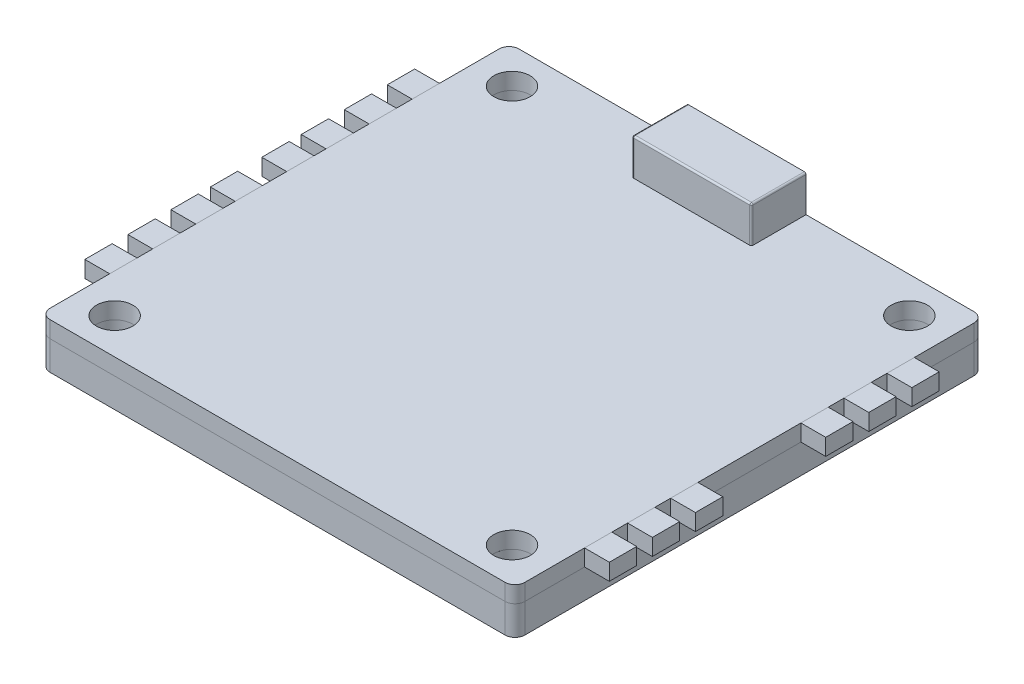
SolidWorks part; units mm, degrees
ref_plane "Front" through (0, 0, 0) normal (0, 0, 1) x (1, 0, 0)
ref_plane "Top" through (0, 0, 0) normal (0, 1, 0) x (1, 0, 0)
ref_plane "Right" through (0, 0, 0) normal (1, 0, 0) x (0, 0, -1)
sketch "Sketch1" plane through (0, 0, 0) normal (0, 1, 0) x (1, 0, 0)
  line L1 (-18.2118, -17.9832) -> (18.2118, -17.9832)
  line L2 (-18.2118, -17.9832) -> (-18.2118, 17.9832)
  line L3 (-18.2118, 17.9832) -> (18.2118, 17.9832)
  line L4 (18.2118, -17.9832) -> (18.2118, 17.9832)
  line L5 (-18.2118, -17.9832) -> (18.2118, 17.9832) construction
  line L6 (-18.2118, 17.9832) -> (18.2118, -17.9832) construction
  line L7 (-15.24, -15.24) -> (15.24, -15.24) construction
  line L8 (-15.24, -15.24) -> (-15.24, 15.24) construction
  line L9 (-15.24, 15.24) -> (15.24, 15.24) construction
  line L10 (15.24, -15.24) -> (15.24, 15.24) construction
  line L11 (-15.24, -15.24) -> (15.24, 15.24) construction
  line L12 (-15.24, 15.24) -> (15.24, -15.24) construction
  circle A0 centre (-15.24, 15.24) radius 1.397
  circle A1 centre (15.24, 15.24) radius 1.397
  circle A2 centre (-15.24, -15.24) radius 1.397
  circle A3 centre (15.24, -15.24) radius 1.397
  point P0 (0, 0)
  point P5 (0, 0)
  dimension "D5" = 2.794
  dimension "D1" = 36.4236
  dimension "D2" = 35.9664
  dimension "D3" = 30.48
  dimension "D4" = 30.48
extrude "Boss-Extrude1" add sketch "Sketch1" along normal blind 1.27
fillet "Fillet1" radius 0.762 4 edges at (-18.2118, 0.635, -17.9832) (18.2118, 0.635, -17.9832) (18.2118, 0.635, 17.9832) (-18.2118, 0.635, 17.9832)
sketch "Sketch6" plane through (0, 0, 0) normal (0, -1, 0) x (1, 0, 0)
  line L4 (-18.2118, 17.2212) -> (-18.2118, -17.2212)
  line L5 (-17.4498, -17.9832) -> (17.4498, -17.9832)
  line L6 (18.2118, -17.2212) -> (18.2118, 17.2212)
  line L7 (17.4498, 17.9832) -> (-17.4498, 17.9832)
  line L8 (-18.2118, 17.2212) -> (-18.2118, -17.2212)
  line L9 (-17.4498, -17.9832) -> (17.4498, -17.9832)
  line L10 (18.2118, -17.2212) -> (18.2118, 17.2212)
  line L11 (17.4498, 17.9832) -> (-17.4498, 17.9832)
  circle A0 centre (-15.24, -15.24) radius 1.397 construction
  circle A1 centre (15.24, -15.24) radius 1.397 construction
  circle A2 centre (15.24, 15.24) radius 1.397 construction
  circle A3 centre (-15.24, 15.24) radius 1.397 construction
  arc A4 (-18.2118, -17.2212) -> (-17.4498, -17.9832) centre (-17.4498, -17.2212) ccw
  arc A5 (17.4498, -17.9832) -> (18.2118, -17.2212) centre (17.4498, -17.2212) ccw
  arc A6 (18.2118, 17.2212) -> (17.4498, 17.9832) centre (17.4498, 17.2212) ccw
  arc A7 (-17.4498, 17.9832) -> (-18.2118, 17.2212) centre (-17.4498, 17.2212) ccw
  arc A8 (-18.2118, -17.2212) -> (-17.4498, -17.9832) centre (-17.4498, -17.2212) ccw
  arc A9 (17.4498, -17.9832) -> (18.2118, -17.2212) centre (17.4498, -17.2212) ccw
  arc A10 (18.2118, 17.2212) -> (17.4498, 17.9832) centre (17.4498, 17.2212) ccw
  arc A11 (-17.4498, 17.9832) -> (-18.2118, 17.2212) centre (-17.4498, 17.2212) ccw
  circle A12 centre (-15.24, -15.24) radius 1.397
  circle A13 centre (15.24, -15.24) radius 1.397
  circle A14 centre (15.24, 15.24) radius 1.397
  circle A15 centre (-15.24, 15.24) radius 1.397
  dimension "D1" = 0
extrude "Electronics Height " add sketch "Sketch6" along normal offset from surface (2.2352 mm away) 3.5052 separate body up to face at (0, 1.27, 0)
sketch "Sketch2" plane through (0, 1.27, 0) normal (0, 1, 0) x (1, 0, 0)
  line L0 (-18.2118, 17.2212) -> (-18.2118, -17.2212) construction
  line L1 (-18.2118, 12.6492) -> (-20.1168, 12.6492)
  line L2 (-18.2118, 12.6492) -> (-18.2118, 10.5532)
  line L3 (-18.2118, 10.5532) -> (-20.1168, 10.5532)
  line L4 (-20.1168, 12.6492) -> (-20.1168, 10.5532)
  line L5 (17.4498, 17.9832) -> (-17.4498, 17.9832) construction
  line L6 (-18.2118, 9.3472) -> (-20.1168, 9.3472)
  line L7 (-18.2118, 9.3472) -> (-18.2118, 7.2512)
  line L8 (-18.2118, 7.2512) -> (-20.1168, 7.2512)
  line L9 (-20.1168, 9.3472) -> (-20.1168, 7.2512)
  line L10 (-18.2118, 6.0452) -> (-20.1168, 6.0452)
  line L11 (-18.2118, 6.0452) -> (-18.2118, 3.9492)
  line L12 (-18.2118, 3.9492) -> (-20.1168, 3.9492)
  line L13 (-20.1168, 6.0452) -> (-20.1168, 3.9492)
  line L14 (0, 0) -> (18.2118, 0) construction
  line L15 (18.2118, -17.2212) -> (18.2118, 17.2212) construction
  line L16 (0, 0) -> (0, 17.9832) construction
  line L17 (20.1168, 6.0452) -> (20.1168, 3.9492)
  line L18 (18.2118, 3.9492) -> (20.1168, 3.9492)
  line L19 (18.2118, 6.0452) -> (18.2118, 3.9492)
  line L20 (18.2118, 6.0452) -> (20.1168, 6.0452)
  line L21 (20.1168, 9.3472) -> (20.1168, 7.2512)
  line L22 (18.2118, 7.2512) -> (20.1168, 7.2512)
  line L23 (18.2118, 9.3472) -> (18.2118, 7.2512)
  line L24 (18.2118, 9.3472) -> (20.1168, 9.3472)
  line L25 (20.1168, 12.6492) -> (20.1168, 10.5532)
  line L26 (18.2118, 10.5532) -> (20.1168, 10.5532)
  line L27 (18.2118, 12.6492) -> (18.2118, 10.5532)
  line L28 (18.2118, 12.6492) -> (20.1168, 12.6492)
  line L29 (18.2118, -12.6492) -> (20.1168, -12.6492)
  line L30 (18.2118, -12.6492) -> (18.2118, -10.5532)
  line L31 (18.2118, -10.5532) -> (20.1168, -10.5532)
  line L32 (20.1168, -12.6492) -> (20.1168, -10.5532)
  line L33 (18.2118, -9.3472) -> (20.1168, -9.3472)
  line L34 (18.2118, -9.3472) -> (18.2118, -7.2512)
  line L35 (18.2118, -7.2512) -> (20.1168, -7.2512)
  line L36 (20.1168, -9.3472) -> (20.1168, -7.2512)
  line L37 (18.2118, -6.0452) -> (20.1168, -6.0452)
  line L38 (18.2118, -6.0452) -> (18.2118, -3.9492)
  line L39 (18.2118, -3.9492) -> (20.1168, -3.9492)
  line L40 (20.1168, -6.0452) -> (20.1168, -3.9492)
  line L41 (-20.1168, -6.0452) -> (-20.1168, -3.9492)
  line L42 (-18.2118, -3.9492) -> (-20.1168, -3.9492)
  line L43 (-18.2118, -6.0452) -> (-18.2118, -3.9492)
  line L44 (-18.2118, -6.0452) -> (-20.1168, -6.0452)
  line L45 (-20.1168, -9.3472) -> (-20.1168, -7.2512)
  line L46 (-18.2118, -7.2512) -> (-20.1168, -7.2512)
  line L47 (-18.2118, -9.3472) -> (-18.2118, -7.2512)
  line L48 (-18.2118, -9.3472) -> (-20.1168, -9.3472)
  line L49 (-20.1168, -12.6492) -> (-20.1168, -10.5532)
  line L50 (-18.2118, -10.5532) -> (-20.1168, -10.5532)
  line L51 (-18.2118, -12.6492) -> (-18.2118, -10.5532)
  line L52 (-18.2118, -12.6492) -> (-20.1168, -12.6492)
  dimension "D1" = 5.334
  dimension "D2" = 2.096
  dimension "D3" = 1.905
  dimension "D4" = 3
extrude "ESC Pins" add sketch "Sketch2" against normal up to surface (1.27 mm away) separate body up to face at (-15.24, 0, 16.637)
sketch "Sketch5" plane through (0, 1.27, 0) normal (0, 1, 0) x (1, 0, 0)
  line L0 (-18.2118, 17.2212) -> (-18.2118, -17.2212) construction
  line L1 (-18.2118, 3.0231) -> (-20.1168, 3.0231)
  line L2 (-18.2118, 3.0231) -> (-18.2118, 0.9271)
  line L3 (-18.2118, 0.9271) -> (-20.1168, 0.9271)
  line L4 (-20.1168, 3.0231) -> (-20.1168, 0.9271)
  line L5 (-20.1168, 0.9271) -> (-20.1168, -0.9271) construction
  line L6 (-18.2118, -0.9271) -> (-20.1168, -0.9271)
  line L7 (-18.2118, -0.9271) -> (-18.2118, -3.0231)
  line L8 (-18.2118, -3.0231) -> (-20.1168, -3.0231)
  line L9 (-20.1168, -0.9271) -> (-20.1168, -3.0231)
  point P10 (-20.1168, 1.9751)
  point P11 (-20.1168, -1.9751)
  point P12 (-19.1643, 0.9271)
  point P13 (-19.1643, -0.9271)
  point P14 (-20.1168, 0)
  dimension "D1" = 1.8542
  dimension "D2" = 2.096
  dimension "D3" = 2.096
  dimension "D4" = 1.905
extrude "Power Pins" add sketch "Sketch5" against normal up to surface (1.27 mm away) separate body up to face at (-15.24, 0, 16.637)
sketch "Sketch3" plane through (0, 0, -17.9832) normal (0, 0, -1) x (-1, 0, 0)
  line L0 (-17.4498, 1.27) -> (17.4498, 1.27) construction
  line L1 (-4.572, 1.27) -> (4.572, 1.27)
  line L2 (-4.572, 1.27) -> (-4.572, 4.064)
  line L3 (-4.572, 4.064) -> (4.572, 4.064)
  line L4 (4.572, 1.27) -> (4.572, 4.064)
  line L5 (0, 3.556) -> (0, 1.524) construction
  line L6 (-3.81, 3.556) -> (3.81, 3.556)
  line L7 (-3.81, 3.556) -> (-3.81, 3.175)
  line L8 (-3.81, 1.524) -> (3.81, 1.524)
  line L9 (3.81, 3.556) -> (3.81, 3.175)
  line L10 (-3.81, 2.667) -> (-4.064, 2.667)
  line L11 (3.81, 2.667) -> (3.81, 1.524)
  line L12 (-3.81, 3.175) -> (-4.064, 3.175)
  line L13 (-4.064, 2.667) -> (-4.064, 3.175)
  line L14 (4.064, 2.667) -> (4.064, 3.175)
  line L15 (3.81, 3.175) -> (4.064, 3.175)
  line L17 (3.81, 2.667) -> (4.064, 2.667)
  line L18 (-3.81, 2.667) -> (-3.81, 1.524)
  point P6 (0, 4.064)
  line M5 (17.4498, 1.27) -> (-17.4498, 1.27)
  dimension "D1" = 9.144
  dimension "D2" = 2.794
  dimension "D3" = 0.508
  dimension "D4" = 0.254
  dimension "D5" = 0.762
  dimension "D6" = 0.762
  dimension "D7" = 0.508
  dimension "D8" = 0.254
  dimension "D9" = 0.381
extrude "Boss-Extrude3" add sketch "Sketch3" against normal blind 4.191 separate body contours L5 L6 L7 L12 L13 L10 L18 L8 | L6 L5 L8 L11 L17 L14 L15 L9 | L4 L3 L2 L18 L10 L13 L12 L7 L6 L9 L15 L14 L17 L11 L8 M5 region at (4.4764, 2.667, -17.9832) region at (-1.9383, 2.5462, -17.9832) region at (1.9383, 2.5462, -17.9832)
extrude "Cut-Extrude1" cut sketch "Sketch3<3>" against normal offset from surface (3.429 mm away) 0.762 contours L5 L6 L7 L12 L13 L10 L18 L8 | L6 L5 L8 L11 L17 L14 L15 L9 region at (-1.9383, 2.5462, -17.9832) region at (1.9383, 2.5462, -17.9832) up to face at (0, 2.667, -13.7922)
sketch "Sketch3<3>" plane through (0, 0, -17.9832) normal (0, 0, -1) x (-1, 0, 0) same geometry as "Sketch3"
sketch "Sketch4" plane through (0, 0, -14.5542) normal (0, 0, -1) x (-1, 0, 0)
  line L0 (-4.064, 2.921) -> (4.064, 2.921) construction
  line L1 (-4.064, 2.667) -> (-4.064, 3.175) construction
  line L2 (4.064, 2.667) -> (4.064, 3.175) construction
  circle A0 centre (-3.1899, 2.921) radius 0.1905
  circle A1 centre (-1.9199, 2.921) radius 0.1905
  circle A2 centre (-0.6499, 2.921) radius 0.1905
  circle A3 centre (0.6201, 2.921) radius 0.1905
  circle A4 centre (1.8901, 2.921) radius 0.1905
  circle A5 centre (3.1601, 2.921) radius 0.1905
  dimension "D1" = 0.381
  dimension "D2" = 6
extrude "Boss-Extrude4" add sketch "Sketch4" along normal blind 3.048
fillet "Fillet2" radius 0.127 5 edges at (-4.572, 2.667, -13.7922) (4.572, 2.667, -13.7922) (-4.572, 4.064, -15.8877) (0, 4.064, -13.7922) (4.572, 4.064, -15.8877)
